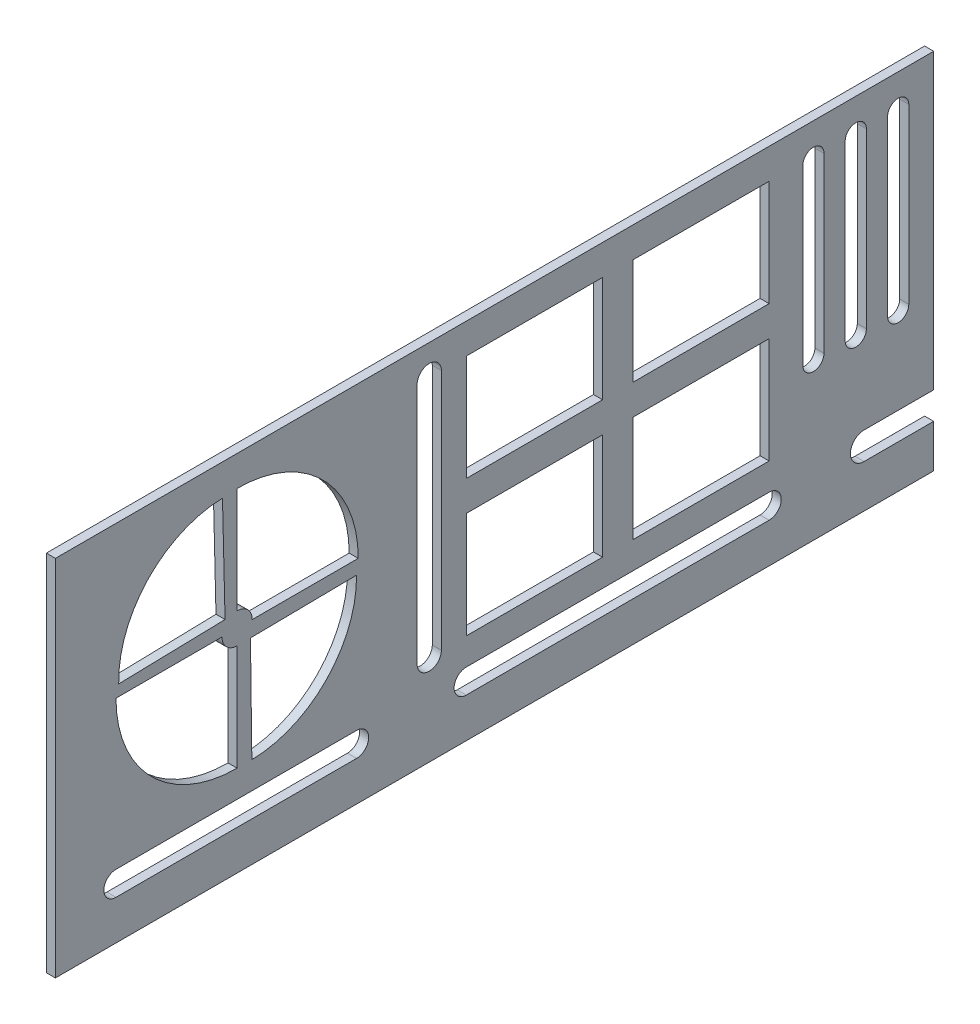
SolidWorks part; units mm, degrees
ref_plane "前视基准面" through (0, 0, 0) normal (0, 0, 1) x (1, 0, 0)
ref_plane "上视基准面" through (0, 0, 0) normal (0, 1, 0) x (1, 0, 0)
ref_plane "右视基准面" through (0, 0, 0) normal (1, 0, 0) x (0, 0, -1)
other "Configuration Table"
sketch "草图1" plane through (0, 0, 0) normal (1, 0, 0) x (0, 0, -1)
  line L1 (-20.9035, 33.3172) -> (269.0965, 33.3172)
  line L2 (-20.9035, 33.3172) -> (-20.9035, -86.6828)
  line L3 (-20.9035, -86.6828) -> (269.0965, -86.6828)
  line L4 (269.0965, 33.3172) -> (269.0965, -86.6828)
  dimension "D1" = 120
  dimension "D2" = 290
extrude "凸台-拉伸1" add sketch "草图1" along normal blind 3
sketch "草图2" plane through (0, 0, 0) normal (-1, 0, 0) x (0, 0, 1)
  line L5 (20.9035, 33.3172) -> (20.9035, -86.6828) construction
  line L6 (-269.0965, 33.3172) -> (20.9035, 33.3172) construction
  line L7 (-79.0965, -16.6828) -> (-44.0965, -16.6828)
  line L8 (-39.0965, -11.6828) -> (-39.0965, 23.3172)
  line L9 (-34.0965, -16.6828) -> (0.9035, -16.6828)
  line L10 (-39.0965, -21.6828) -> (-39.0965, -56.6828)
  line L11 (-243.761, -53.9722) -> (-269.0965, -53.9722)
  line L12 (-269.0965, -86.6828) -> (-269.0965, 33.3172) construction
  line L13 (-269.0965, -53.9722) -> (-269.0965, -62.9722)
  line L14 (-269.0965, -62.9722) -> (-243.761, -62.9722)
  arc A0 (-39.0965, -56.6828) -> (0.9035, -16.6828) centre (-39.0965, -16.6828) ccw
  arc A1 (-39.0965, -11.6828) -> (-44.0965, -16.6828) centre (-39.0965, -16.6828) ccw
  arc A2 (-79.0965, -16.6828) -> (-39.0965, 23.3172) centre (-39.0965, -16.6828) cw
  arc A3 (-39.0965, -56.6828) -> (0.9035, -16.6828) centre (-39.0965, -16.6828) ccw
  arc A4 (-39.0965, 23.3172) -> (-79.0965, -16.6828) centre (-39.0965, -16.6828) ccw
  arc A5 (-44.0965, -16.6828) -> (-39.0965, -11.6828) centre (-39.0965, -16.6828) cw
  arc A6 (-34.0965, -16.6828) -> (-39.0965, -21.6828) centre (-39.0965, -16.6828) cw
  arc A7 (-39.0965, -21.6828) -> (-34.0965, -16.6828) centre (-39.0965, -16.6828) ccw
  circle A8 centre (-243.761, -58.4722) radius 4.5
  dimension "D4" = 60
  dimension "D5" = 50
extrude "切除-拉伸5" cut sketch "草图2" against normal blind 10 contours A2 L7 A1 L8 | L9 A6 L10 A0 region at (0, 0.5296, -56.3088) region at (0, -33.8951, -21.8842)
sketch "草图3" plane through (0, 0, 0) normal (-1, 0, 0) x (0, 0, 1)
  line L0 (-78.5312, -21.2041) -> (-43.5067, -21.6583)
  line L1 (-43.5067, -21.6583) -> (-43.961, -56.6828)
  line L2 (-34.266, 22.9335) -> (-35.1197, -12.1862)
  line L3 (-35.1197, -12.1862) -> (0, -13.0399)
  arc A0 (-34.266, 22.9335) -> (0, -13.0399) centre (-35.1197, -12.1862) cw
  arc A1 (-78.5312, -21.2041) -> (-43.961, -56.6828) centre (-43.5067, -21.6583) ccw
extrude "切除-拉伸6" cut sketch "草图3" against normal blind 3
sketch "草图4" plane through (0, 0, 0) normal (-1, 0, 0) x (0, 0, 1)
  line L0 (-269.0965, 33.3172) -> (20.9035, 33.3172) construction
  line L1 (-214.7588, 23.3172) -> (-114.7588, 23.3172)
  line L2 (-214.7588, 23.3172) -> (-214.7588, -56.6828)
  line L3 (-214.7588, -56.6828) -> (-114.7588, -56.6828)
  line L4 (-114.7588, 23.3172) -> (-114.7588, -56.6828)
  line L5 (-214.7588, -16.6828) -> (-114.7588, -16.6828) construction
  line L6 (-214.7588, -11.6828) -> (-114.7588, -11.6828)
  line L7 (-214.7588, -21.6828) -> (-114.7588, -21.6828)
  line L8 (-164.7588, 23.3172) -> (-164.7588, -56.6828) construction
  line L9 (-159.7588, 23.3172) -> (-159.7588, -56.6828)
  line L10 (-169.7588, 23.3172) -> (-169.7588, -56.6828)
  arc A0 (-214.7588, -11.6828) -> (-214.7588, -21.6828) centre (-214.7588, -16.6828) ccw
  arc A1 (-114.7588, -21.6828) -> (-114.7588, -11.6828) centre (-114.7588, -16.6828) ccw
  arc A2 (-159.7588, 23.3172) -> (-169.7588, 23.3172) centre (-164.7588, 23.3172) ccw
  arc A3 (-169.7588, -56.6828) -> (-159.7588, -56.6828) centre (-164.7588, -56.6828) ccw
  point P8 (-164.7588, -16.6828)
  point P13 (-164.7588, -16.6828)
  dimension "D1" = 80
  dimension "D2" = 100
  dimension "D3" = 10
extrude "切除-拉伸10" cut sketch "草图4" against normal blind 10 contours L10 L1 L2 L6 | L1 L9 L6 L4 | L7 L9 L3 L4 | L10 L7 L2 L3 region at (0, 5.8172, -192.2588) region at (0, 5.8172, -137.2588) region at (0, -39.1828, -192.2588) region at (0, -39.1828, -137.2588)
sketch "草图5" plane through (0, 0, 0) normal (-1, 0, 0) x (0, 0, 1)
  line L0 (-243.3757, 22.2378) -> (-243.3757, -34.9202) construction
  line L1 (-239.8757, 22.2378) -> (-239.8757, -34.9202)
  line L2 (-246.8757, 22.2378) -> (-246.8757, -34.9202)
  line L3 (-229.3757, 22.2378) -> (-229.3757, -34.9202) construction
  line L4 (-225.8757, 22.2378) -> (-225.8757, -34.9202)
  line L5 (-232.8757, 22.2378) -> (-232.8757, -34.9202)
  line L6 (-257.3757, 22.2378) -> (-257.3757, -34.9202) construction
  line L7 (-253.8757, 22.2378) -> (-253.8757, -34.9202)
  line L8 (-260.8757, 22.2378) -> (-260.8757, -34.9202)
  arc A0 (-239.8757, 22.2378) -> (-246.8757, 22.2378) centre (-243.3757, 22.2378) ccw
  arc A1 (-246.8757, -34.9202) -> (-239.8757, -34.9202) centre (-243.3757, -34.9202) ccw
  arc A2 (-225.8757, 22.2378) -> (-232.8757, 22.2378) centre (-229.3757, 22.2378) ccw
  arc A3 (-232.8757, -34.9202) -> (-225.8757, -34.9202) centre (-229.3757, -34.9202) ccw
  arc A4 (-253.8757, 22.2378) -> (-260.8757, 22.2378) centre (-257.3757, 22.2378) ccw
  arc A5 (-260.8757, -34.9202) -> (-253.8757, -34.9202) centre (-257.3757, -34.9202) ccw
  point P2 (-243.3757, -6.3412)
  point P9 (-229.3757, -6.3412)
  point P14 (-257.3757, -6.3412)
  point P21 (0, 0)
  dimension "D1" = 7
  dimension "D2" = 7
  dimension "D3" = 3.5
  dimension "D4" = 7
  dimension "D5" = 3.5
extrude "切除-拉伸11" cut sketch "草图5" against normal blind 3
sketch "草图6" plane through (0, 0, 0) normal (-1, 0, 0) x (0, 0, 1)
  line L0 (-214.7588, -69.6095) -> (-114.7588, -69.6095) construction
  line L1 (-214.7588, -65.6095) -> (-114.7588, -65.6095)
  line L2 (-214.7588, -73.6095) -> (-114.7588, -73.6095)
  line L3 (-102.5416, 23.3172) -> (-102.5416, -56.6828) construction
  line L4 (-98.5416, 23.3172) -> (-98.5416, -56.6828)
  line L5 (-106.5416, 23.3172) -> (-106.5416, -56.6828)
  line L6 (0.9035, -69.6095) -> (-78.5341, -69.6095) construction
  line L7 (0.9035, -73.6095) -> (-78.5341, -73.6095)
  line L8 (0.9035, -65.6095) -> (-78.5341, -65.6095)
  arc A0 (-214.7588, -65.6095) -> (-214.7588, -73.6095) centre (-214.7588, -69.6095) ccw
  arc A1 (-114.7588, -73.6095) -> (-114.7588, -65.6095) centre (-114.7588, -69.6095) ccw
  arc A2 (-98.5416, 23.3172) -> (-106.5416, 23.3172) centre (-102.5416, 23.3172) ccw
  arc A3 (-106.5416, -56.6828) -> (-98.5416, -56.6828) centre (-102.5416, -56.6828) ccw
  arc A4 (0.9035, -73.6095) -> (0.9035, -65.6095) centre (0.9035, -69.6095) ccw
  arc A5 (-78.5341, -65.6095) -> (-78.5341, -73.6095) centre (-78.5341, -69.6095) ccw
  point P2 (-164.7588, -69.6095)
  point P9 (-102.5416, -16.6828)
  point P16 (-38.8153, -69.6095)
extrude "切除-拉伸12" cut sketch "草图6" against normal blind 3
sketch "草图7" plane through (0, 0, 0) normal (-1, 0, 0) x (0, 0, 1)
  line L0 (-246.0965, -63.501) -> (-269.0965, -63.501)
  line L1 (-269.0965, -86.6828) -> (-269.0965, 33.3172) construction
  line L2 (-246.0965, -72.501) -> (-269.0965, -72.501)
  line L3 (-269.0965, -63.501) -> (-269.0965, -72.501)
  circle A0 centre (-246.0965, -68.001) radius 4.5
  dimension "D1" = 23
extrude "切除-拉伸13" cut sketch "草图7" against normal blind 3 contours A0 L0 L3 L2 | A0 region at (0, -68.001, -259.3378) region at (0, -68.001, -246.0965)
